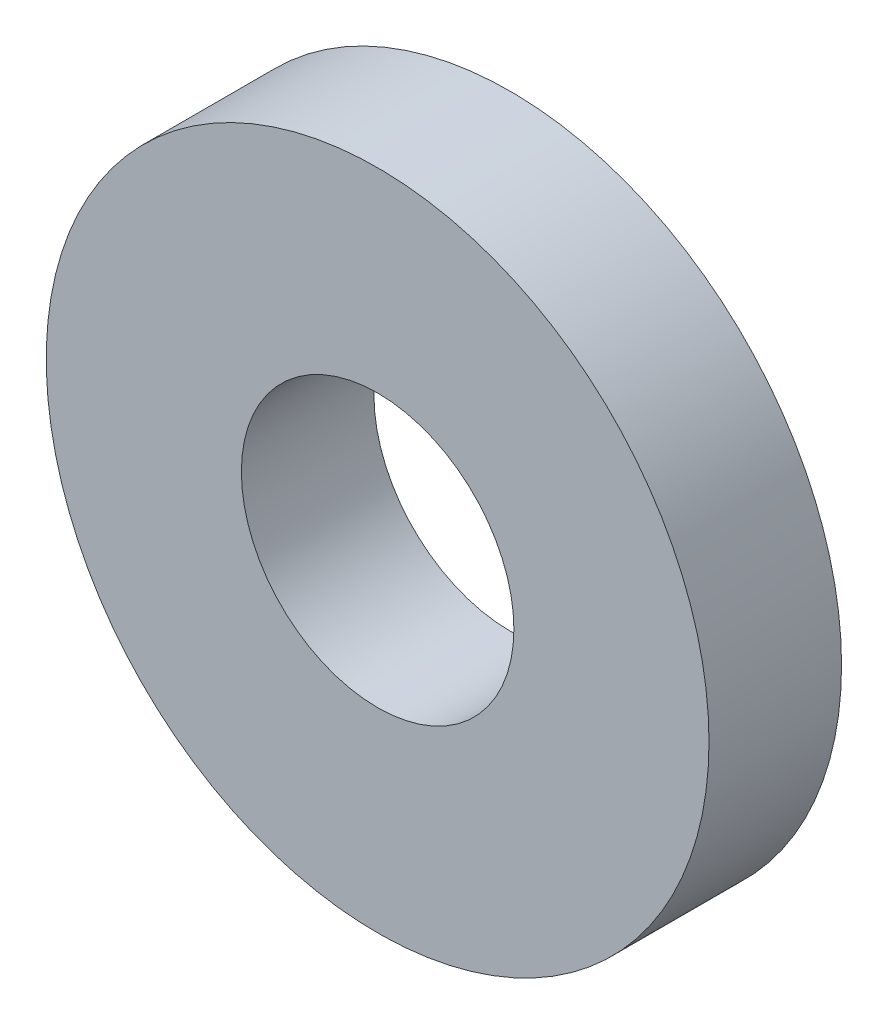
SolidWorks part; units mm, degrees
material "Nylon 6/10"
ref_plane "Front Plane" through (0, 0, 0) normal (0, 0, 1) x (1, 0, 0)
ref_plane "Top Plane" through (0, 0, 0) normal (0, 1, 0) x (1, 0, 0)
ref_plane "Right Plane" through (0, 0, 0) normal (1, 0, 0) x (0, 0, -1)
sketch "Sketch1" plane through (0, 0, 0) normal (0, 0, 1) x (1, 0, 0)
  circle A0 centre (0, 0) radius 7.9375
  circle A1 centre (0, 0) radius 3.2639
  dimension "OD" = 15.875
  dimension "ID" = 6.5278
extrude "Extrude1" add sketch "Sketch1" along normal mid plane 3.175
sketch "Sketch2" plane through (0, 0, 0) normal (1, 0, 0) x (0, 0, -1)
  line L0 (-1.5875, -3.2639) -> (1.5875, -3.2639) construction
  line L3 (1.5875, 3.2639) -> (-1.5875, 3.2639) construction
  line L5 (-1.5875, -3.2639) -> (1.5875, -3.2639)
  line L6 (1.5875, 3.2639) -> (-1.5875, 3.2639)
sketch "Sketch4" plane through (0, 0, 1.5875) normal (0, 0, 1) x (1, 0, 0)
  line L0 (0, 0) -> (-2.3079, 2.3079)
  line L1 (0, -3.4925) -> (0, 3.4925) construction
  circle A0 centre (0, 0) radius 3.2639 construction
  dimension "D1" = 45
